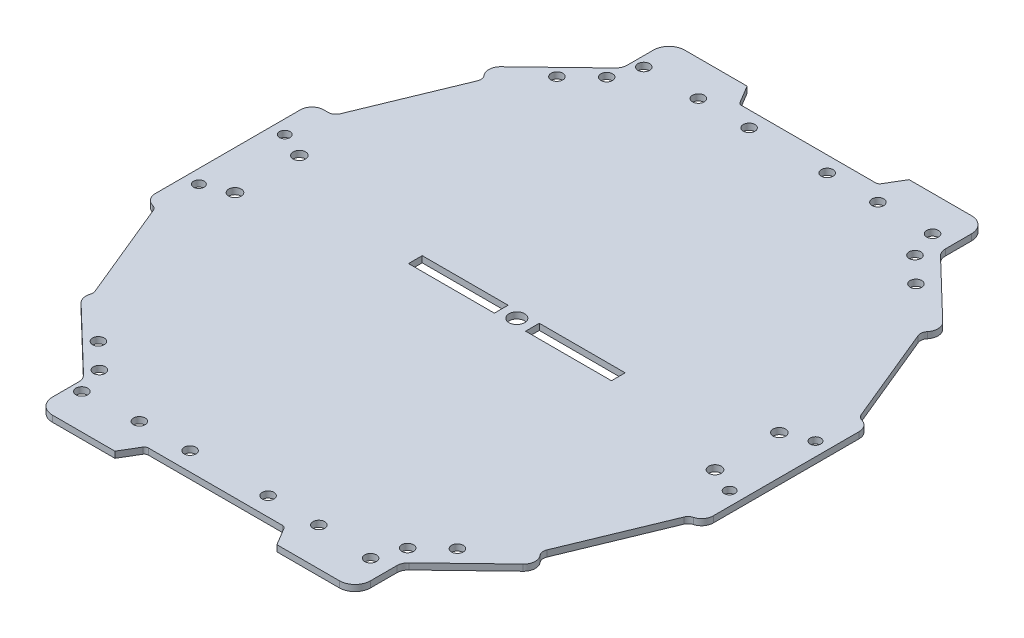
SolidWorks part; units mm, degrees
ref_plane "Front Plane" through (0, 0, 0) normal (0, 0, 1) x (1, 0, 0)
ref_plane "Top Plane" through (0, 0, 0) normal (0, 1, 0) x (1, 0, 0)
ref_plane "Right Plane" through (0, 0, 0) normal (1, 0, 0) x (0, 0, -1)
ref_plane "Plane1"
sketch "Sketch1" plane through (0, 0, 0) normal (0, 1, 0) x (-1, 0, 0)
  line L0 (59.7752, 259.0599) -> (56.7752, 264.0599)
  line L1 (56.7752, 264.0599) -> (36.7752, 264.0599)
  line L2 (36.7752, 264.0599) -> (36.7752, 252.0599)
  line L3 (36.7752, 252.0599) -> (18.7553, 234.7311)
  line L4 (18.7553, 234.7311) -> (21.5279, 231.8479)
  line L5 (21.5279, 231.8479) -> (10.2752, 204.5599)
  line L6 (10.2752, 204.5599) -> (7.2752, 204.5599)
  line L7 (7.2752, 204.5599) -> (7.2752, 183.0599)
  line L8 (7.2752, 183.0599) -> (7.2752, 161.5599)
  line L9 (7.2752, 161.5599) -> (10.2752, 161.5599)
  line L10 (10.2752, 161.5599) -> (21.5279, 134.2718)
  line L11 (21.5279, 134.2718) -> (18.7553, 131.3886)
  line L12 (18.7553, 131.3886) -> (36.7752, 114.0599)
  line L13 (36.7752, 114.0599) -> (36.7752, 102.0599)
  line L14 (36.7752, 102.0599) -> (56.7752, 102.0599)
  line L15 (56.7752, 102.0599) -> (59.7752, 107.0599)
  line L16 (59.7752, 107.0599) -> (76.2975, 107.0599)
  line L17 (76.2975, 107.0599) -> (95.2975, 107.0599)
  line L18 (95.2975, 107.0599) -> (98.2975, 102.0599)
  line L19 (98.2975, 102.0599) -> (118.2975, 102.0599)
  line L20 (118.2975, 102.0599) -> (118.2975, 114.0599)
  line L21 (118.2975, 114.0599) -> (136.3173, 131.3886)
  line L22 (136.3173, 131.3886) -> (133.5447, 134.2718)
  line L23 (133.5447, 134.2718) -> (144.7975, 161.5599)
  line L24 (144.7975, 161.5599) -> (150.2752, 161.5599)
  line L25 (150.2752, 161.5599) -> (150.2752, 183.0599)
  line L26 (150.2752, 183.0599) -> (150.2752, 204.5599)
  line L27 (150.2752, 204.5599) -> (147.2752, 204.5599)
  line L28 (147.2752, 204.5599) -> (136.0224, 231.8479)
  line L29 (136.0224, 231.8479) -> (137.6046, 233.4932)
  line L30 (137.6046, 233.4932) -> (118.2975, 252.0599)
  line L31 (118.2975, 252.0599) -> (118.2975, 264.0599)
  line L32 (118.2975, 264.0599) -> (98.2975, 264.0599)
  line L33 (98.2975, 264.0599) -> (95.2975, 259.0599)
  line L34 (95.2975, 259.0599) -> (76.2975, 259.0599)
  line L35 (76.2975, 259.0599) -> (59.7752, 259.0599)
  line L38 (76.2975, 259.0599) -> (76.2975, 107.0599) construction
  line L39 (150.2752, 183.0599) -> (7.2752, 183.0599) construction
  line L41 (72.2975, 184.818) -> (50.2975, 184.818)
  line L44 (72.2975, 184.818) -> (72.2975, 181.3017)
  line L45 (72.2975, 181.3017) -> (50.2975, 181.3017)
  line L46 (50.2975, 184.818) -> (50.2975, 181.3017)
  line L47 (72.2975, 184.818) -> (50.2975, 181.3017) construction
  line L48 (72.2975, 181.3017) -> (50.2975, 184.818) construction
  line L49 (102.2975, 184.818) -> (80.2975, 184.818)
  line L50 (102.2975, 184.818) -> (102.2975, 181.3017)
  line L51 (102.2975, 181.3017) -> (80.2975, 181.3017)
  line L52 (80.2975, 184.818) -> (80.2975, 181.3017)
  line L53 (102.2975, 184.818) -> (80.2975, 181.3017) construction
  line L54 (102.2975, 181.3017) -> (80.2975, 184.818) construction
  line L85 (91.8838, 199.6325) -> (91.9874, 199.5289)
  line L87 (95.3777, 196.1387) -> (95.4193, 196.097)
  circle A0 centre (55.7752, 111.0599) radius 1.5
  circle A1 centre (39.2752, 118.0599) radius 1.5
  circle A4 centre (17.2752, 174.8099) radius 1.6
  circle A10 centre (76.2975, 183.0599) radius 2
  circle A22 centre (41.7752, 255.0599) radius 1.5
  circle A23 centre (39.2752, 248.0599) radius 1.5
  circle A24 centre (10.7752, 194.0599) radius 1.35
  circle A25 centre (88.7752, 111.0599) radius 1.5
  circle A27 centre (115.7752, 111.0599) radius 1.5
  circle A28 centre (118.2752, 118.0599) radius 1.5
  circle A29 centre (140.2752, 174.8099) radius 1.6
  circle A30 centre (115.7752, 255.0599) radius 1.5
  circle A31 centre (88.7752, 254.3099) radius 1.5
  circle A32 centre (140.2752, 191.3099) radius 1.6
  circle A33 centre (146.7752, 194.0599) radius 1.35
  circle A53 centre (101.7752, 254.3099) radius 1.5
  circle A54 centre (118.2752, 248.0599) radius 1.5
  circle A55 centre (146.7752, 172.0599) radius 1.35
  circle A57 centre (101.7752, 111.0599) radius 1.5
  circle A69 centre (17.2752, 191.3099) radius 1.6
  circle A71 centre (55.7752, 254.3099) radius 1.5
  circle A73 centre (68.7752, 254.3099) radius 1.5
  circle A74 centre (10.7752, 172.0599) radius 1.35
  circle A76 centre (68.7752, 111.0599) radius 1.5
  circle A77 centre (41.7752, 111.0599) radius 1.5
  circle A82 centre (32.7752, 124.3099) radius 1.5
  circle A86 centre (124.7752, 241.8099) radius 1.5
  circle A87 centre (32.7752, 241.8099) radius 1.5
  circle A91 centre (124.7752, 124.3099) radius 1.5
  point P41 (150.2752, 193.8099)
  point P43 (61.2975, 183.0599)
  point P50 (91.2975, 183.0599)
  point P55 (0, 0)
  point P56 (0, 0)
  point P57 (0, 0)
  dimension "D1" = 143
  dimension "D2" = 162
  dimension "D3" = 30
  dimension "D4" = 15
extrude "Extrusion1" add sketch "Sketch1" along normal blind 1.6
fillet "Fillet1" radius 1 4 edges at (-95.2975, 0.8, 107.0599) (-59.7752, 0.8, 107.0599) (-59.7752, 0.8, 259.0599) (-95.2975, 0.8, 259.0599)
fillet "Fillet2" radius 4 4 edges at (-118.2975, 0.8, 102.0599) (-36.7752, 0.8, 102.0599) (-118.2975, 0.8, 264.0599) (-36.7752, 0.8, 264.0599)
fillet "Fillet3" radius 3 4 edges at (-118.2975, 0.8, 114.0599) (-36.7752, 0.8, 114.0599) (-36.7752, 0.8, 252.0599) (-118.2975, 0.8, 252.0599)
fillet "Fillet4" radius 3 1 edges at (-137.6046, 0.8, 233.4932)
fillet "Fillet5" radius 2 1 edges at (-136.0224, 0.8, 231.8479)
fillet "Fillet6" radius 2 1 edges at (-21.5279, 0.8, 231.8479)
fillet "Fillet7" radius 3 1 edges at (-18.7553, 0.8, 234.7311)
fillet "Fillet8" radius 3 2 edges at (-136.3173, 0.8, 131.3886) (-18.7553, 0.8, 131.3886)
fillet "Fillet9" radius 2 2 edges at (-21.5279, 0.8, 134.2718) (-133.5447, 0.8, 134.2718)
fillet "Fillet10" radius 2 4 edges at (-10.2752, 0.8, 161.5599) (-10.2752, 0.8, 204.5599) (-147.2752, 0.8, 204.5599) (-144.7975, 0.8, 161.5599)
fillet "Fillet11" radius 3 4 edges at (-150.2752, 0.8, 161.5599) (-150.2752, 0.8, 204.5599) (-7.2752, 0.8, 204.5599) (-7.2752, 0.8, 161.5599)
